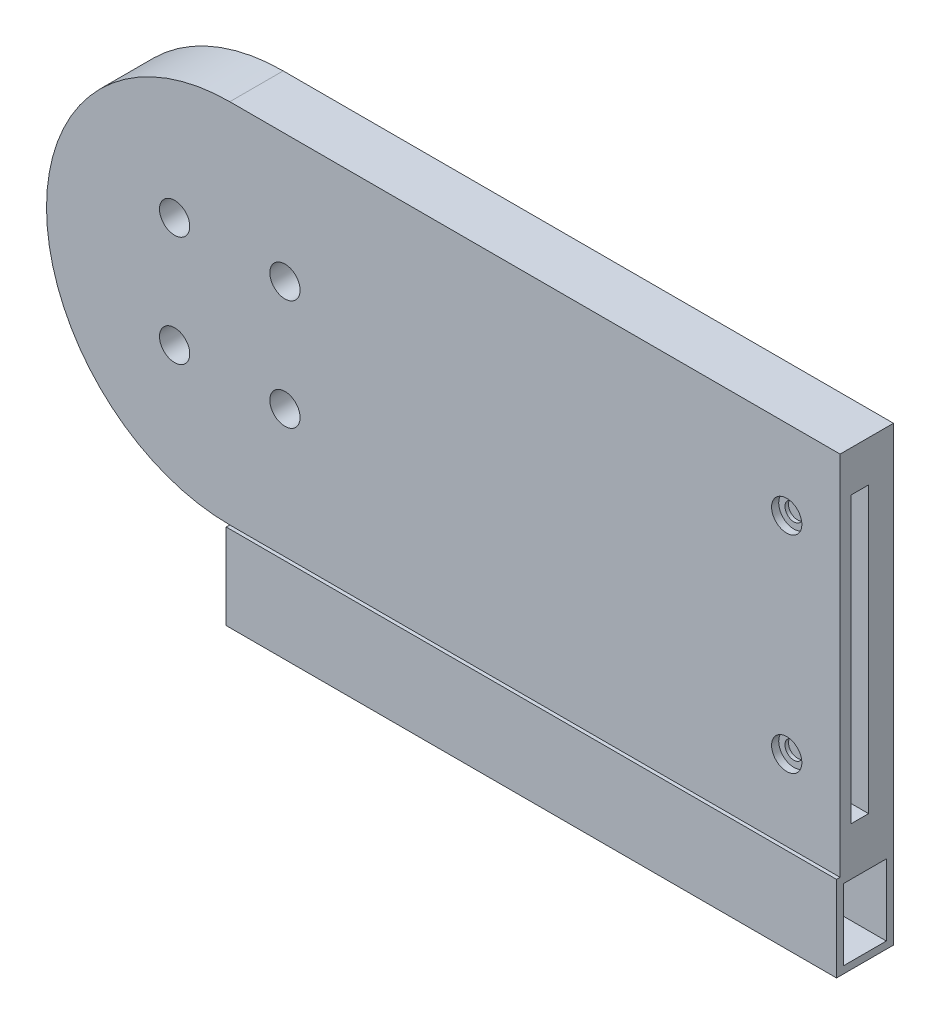
SolidWorks part; units mm, degrees
ref_plane "Alzado" through (0, 0, 0) normal (0, 0, 1) x (1, 0, 0)
ref_plane "Planta" through (0, 0, 0) normal (0, 1, 0) x (1, 0, 0)
ref_plane "Vista lateral" through (0, 0, 0) normal (1, 0, 0) x (0, 0, -1)
sketch "Croquis1" plane through (0, 0, 0) normal (0, 0, 1) x (1, 0, 0)
  line L5 (-51.5, -51.5) -> (51.5, 51.5) construction
  line L6 (-51.5, 51.5) -> (51.5, -51.5) construction
  line L7 (-51.5, -51.5) -> (51.5, -51.5)
  line L8 (-51.5, -51.5) -> (-51.5, 51.5)
  line L9 (-51.5, 51.5) -> (51.5, 51.5)
  line L10 (51.5, -51.5) -> (51.5, 51.5)
  line L11 (-51.5, -51.5) -> (51.5, 51.5) construction
  line L12 (-51.5, 51.5) -> (51.5, -51.5) construction
  circle A0 centre (15.5, 15.5) radius 2.5
  circle A1 centre (-15.5, 15.5) radius 2.5
  circle A2 centre (-15.5, -15.5) radius 2.5
  circle A3 centre (15.5, -15.5) radius 2.5
  point P0 (0, 0)
  point P18 (0, 0)
  dimension "D3" = 5
  dimension "D4" = 5
  dimension "D5" = 5
  dimension "D6" = 5
  dimension "D1" = 103
  dimension "D2" = 103
  dimension "D7" = 31
extrude "Saliente-Extruir1" add sketch "Croquis1" along normal blind 15
fillet "Redondeo2" radius 51.5 2 edges at (-51.5, -51.5, 7.5) (-51.5, 51.5, 7.5)
sketch "Croquis2" plane through (51.5, 0, 0) normal (1, 0, 0) x (0, 0, -1)
  line L4 (0, -51.5) -> (0, 51.5)
  line L5 (0, 51.5) -> (-15, 51.5)
  line L6 (-15, 51.5) -> (-15, -51.5)
  line L7 (-15, -51.5) -> (0, -51.5)
  line L8 (0, -51.5) -> (0, 51.5)
  line L9 (0, 51.5) -> (-15, 51.5)
  line L10 (-15, 51.5) -> (-15, -51.5)
  line L11 (-15, -51.5) -> (0, -51.5)
  dimension "D1" = 0
extrude "Saliente-Extruir2" add sketch "Croquis2" along normal blind 120
sketch "Croquis3" plane through (0, 0, 15) normal (0, 0, 1) x (1, 0, 0)
  circle A0 centre (-15.5, 15.5) radius 4.25
  circle A1 centre (15.5, 15.5) radius 4.25
  circle A2 centre (15.5, -15.5) radius 4.25
  circle A3 centre (-15.5, -15.5) radius 4.25
  dimension "D1" = 8.5
  dimension "D2" = 8.5
  dimension "D3" = 8.5
  dimension "D4" = 8.5
extrude "Cortar-Extruir1" cut sketch "Croquis3" against normal blind 8
sketch "Croquis4" plane through (171.5, 0, 0) normal (1, 0, 0) x (0, 0, -1)
  line L0 (-15, 0) -> (-40.1714, 0) construction
  line L1 (-15, 51.5) -> (-15, -51.5) construction
  line L2 (-15, -19) -> (-15, -25)
  line L3 (-15, 25) -> (-23, 25)
  line L4 (-15, 25) -> (-15, 19)
  line L5 (-15, -25) -> (-23, -25)
  line L6 (-23, 25) -> (-23, -25)
  line L7 (-15, 19) -> (-19, 19)
  line L9 (-15, -19) -> (-19, -19)
  line L10 (-19, 19) -> (-19, -19)
  point P10 (-23, 0)
  point P15 (-19, 0)
  dimension "D1" = 50
  dimension "D2" = 8
  dimension "D3" = 38
  dimension "D4" = 4
extrude "Saliente-Extruir3" add sketch "Croquis4" against normal up to vertex (223 mm away) up to point (-51.5, 0, 15)
sketch "Croquis5" plane through (0, 0, 0) normal (0, 0, -1) x (-1, 0, 0)
  line L5 (40.9309, 31.2556) -> (61.4226, 30.3153)
  line L6 (61.4226, 30.3153) -> (63.075, -35.0569)
  line L7 (63.075, -35.0569) -> (38.432, -34.2816)
  arc A0 (0, -51.5) -> (51.5, 0) centre (0, 0) ccw construction
  arc A1 (51.5, 0) -> (0, 51.5) centre (0, 0) ccw construction
  arc A2 (38.432, -34.2816) -> (51.5, 0) centre (0, 0) ccw
  arc A3 (51.5, 0) -> (40.9309, 31.2556) centre (0, 0) ccw
extrude "Cortar-Extruir2" cut sketch "Croquis5" against normal through all both and the other way through all
fillet "Redondeo3" radius 10 2 edges at (63.2375, -25, 15) (63.2375, 25, 15)
fillet "Redondeo4" radius 10 2 edges at (63.2375, -25, 23) (63.2375, 25, 23)
sketch "Croquis6" plane through (0, 0, 23) normal (0, 0, 1) x (1, 0, 0)
  arc A0 (13.0891, 19) -> (17.9109, 19) centre (15.5, 15.5) ccw construction
  arc A1 (17.9109, -19) -> (13.0891, -19) centre (15.5, -15.5) ccw construction
  arc A2 (-13.0891, -19) -> (-17.9109, -19) centre (-15.5, -15.5) ccw construction
  arc A3 (-17.9109, 19) -> (-13.0891, 19) centre (-15.5, 15.5) ccw construction
  arc A4 (13.0891, 19) -> (17.9109, 19) centre (15.5, 15.5) ccw construction
  arc A5 (17.9109, -19) -> (13.0891, -19) centre (15.5, -15.5) ccw construction
  arc A6 (-13.0891, -19) -> (-17.9109, -19) centre (-15.5, -15.5) ccw construction
  arc A7 (-17.9109, 19) -> (-13.0891, 19) centre (-15.5, 15.5) ccw construction
  circle A8 centre (15.5, 15.5) radius 4.25
  circle A9 centre (-15.5, 15.5) radius 4.25
  circle A10 centre (15.5, -15.5) radius 4.25
  circle A11 centre (-15.5, -15.5) radius 4.25
extrude "Cortar-Extruir3" cut sketch "Croquis6" against normal up to next and the other way through all
sketch "Croquis7" plane through (171.5, 0, 0) normal (1, 0, 0) x (0, 0, -1)
  line L0 (0, 0) -> (-23, 0) construction
  line L1 (-23, 18.798) -> (-23, -18.798) construction
  line L3 (-12, 40) -> (-7, 40)
  line L4 (-12, 40) -> (-12, -40)
  line L5 (-12, -40) -> (-7, -40)
  line L6 (-7, 40) -> (-7, -40)
  line L7 (-12, 40) -> (-7, -40) construction
  line L8 (-12, -40) -> (-7, 40) construction
  line L9 (0, -51.5) -> (0, 51.5) construction
  point P5 (-9.5, 0)
  dimension "D1" = 5
  dimension "D2" = 80
  dimension "D3" = 7
extrude "Cortar-Extruir4" cut sketch "Croquis7" against normal blind 40 and the other way through all
sketch "Croquis8" plane through (0, 0, 23) normal (0, 0, 1) x (1, 0, 0)
  line L0 (0, 0) -> (0, -128.916) construction
  line L1 (0, 0) -> (-190.5099, 0) construction
  line L2 (0, 0) -> (0, 141.6766) construction
sketch "Croquis10" plane through (0, 0, 23) normal (0, 0, 1) x (1, 0, 0)
  line L0 (171.5, 19) -> (171.5, -19) construction
  line L1 (171.5, 19) -> (171.5, -19) construction
  line L2 (171.5, -40) -> (171.5, 40) construction
  line L3 (171.5, -40) -> (171.5, 40) construction
  line L4 (171.5, 40) -> (18.9528, 40) construction
  line L5 (171.5, 18.798) -> (122.7487, 18.798) construction
  line L6 (23.8745, 0) -> (125.8247, 0) construction
  line L7 (156.5, 40) -> (156.5, 18.798) construction
  line L8 (171.5, 18.798) -> (18.1807, 18.798) construction
  line L10 (171.5, 26.798) -> (171.5, 34.798) construction
  circle A0 centre (156.5, 29) radius 4.25
  circle A1 centre (156.5, -29) radius 4.25
  dimension "D1" = 8.5
  dimension "D2" = 15
  dimension "D3" = 58
extrude "Cortar-Extruir5" cut sketch "Croquis10" against normal blind 10
sketch "Croquis11" plane through (0, 0, 13) normal (0, 0, 1) x (1, 0, 0)
  circle A0 centre (156.5, 29) radius 2.5
  circle A1 centre (156.5, 29) radius 4.25
  circle A2 centre (156.5, 29) radius 4.25 construction
  circle A3 centre (156.5, -29) radius 4.25
  circle A4 centre (156.5, -29) radius 4.25 construction
  circle A5 centre (156.5, -29) radius 2.5
  dimension "D3" = 5
  dimension "D4" = 5
  dimension "D1" = 0
  dimension "D2" = 0
extrude "Cortar-Extruir6" cut sketch "Croquis11" against normal through all
sketch "Croquis12" plane through (171.5, 0, 0) normal (1, 0, 0) x (0, 0, -1)
  line L0 (0, 0) -> (-72.5569, 0) construction
  line L1 (-16, 51.5) -> (-16, 75.5) construction
  line L2 (-2, -53.5) -> (-14, -53.5)
  line L3 (-2, -53.5) -> (-2, -73.5)
  line L4 (-2, -73.5) -> (-14, -73.5)
  line L5 (-14, -53.5) -> (-14, -73.5)
  line L6 (0, -51.5) -> (-16, -51.5)
  line L7 (0, -51.5) -> (0, -75.5)
  line L8 (0, -75.5) -> (-16, -75.5)
  line L9 (-16, -51.5) -> (-16, -75.5)
  line L10 (0, 75.5) -> (-16, 75.5) construction
  line L11 (0, 51.5) -> (0, 75.5) construction
  line L12 (0, 51.5) -> (-16, 51.5) construction
  line L13 (-14, 53.5) -> (-14, 73.5) construction
  line L14 (-2, 73.5) -> (-14, 73.5) construction
  line L15 (-2, 53.5) -> (-2, 73.5) construction
  line L16 (-2, 53.5) -> (-14, 53.5) construction
  dimension "D1" = 12
  dimension "D2" = 20
  dimension "D3" = 16
  dimension "D4" = 24
  dimension "D5" = 2
  dimension "D6" = 2
extrude "Saliente-Extruir4" add sketch "Croquis12" against normal up to vertex (171.5 mm away) up to point (0, -51.5, 0)
sketch "Croquis13" plane through (0, 0, 0) normal (0, 0, -1) x (-1, 0, 0)
  line L1 (-156.5, 24.3812) -> (-152.5, 26.6906)
  line L2 (-152.5, 26.6906) -> (-152.5, 31.3094)
  line L3 (-152.5, 31.3094) -> (-156.5, 33.6188)
  line L4 (-156.5, 33.6188) -> (-160.5, 31.3094)
  line L5 (-160.5, 31.3094) -> (-160.5, 26.6906)
  line L6 (-160.5, 26.6906) -> (-156.5, 24.3812)
  line L7 (-152.5, -26.6906) -> (-156.5, -24.3812)
  line L8 (-156.5, -24.3812) -> (-160.5, -26.6906)
  line L9 (-160.5, -26.6906) -> (-160.5, -31.3094)
  line L10 (-160.5, -31.3094) -> (-156.5, -33.6188)
  line L11 (-156.5, -33.6188) -> (-152.5, -31.3094)
  line L12 (-152.5, -31.3094) -> (-152.5, -26.6906)
  circle A0 centre (-156.5, 29) radius 4 construction
  circle A1 centre (-156.5, -29) radius 4 construction
  dimension "D1" = 8
  dimension "D2" = 8
extrude "Cortar-Extruir7" cut sketch "Croquis13" against normal blind 4
sketch "Croquis14" plane through (0, 0, 23) normal (0, 0, 1) x (1, 0, 0)
  line L1 (171.5, -51.5) -> (-71.0835, -51.5)
  line L2 (171.5, -51.5) -> (171.5, 52.3672)
  line L3 (171.5, 52.3672) -> (-71.0835, 52.3672)
  line L4 (-71.0835, -51.5) -> (-71.0835, 52.3672)
extrude "Cortar-Extruir8" cut sketch "Croquis14" against normal up to surface (8 mm away) up to face at (75.8198, 44.1467, 15)
